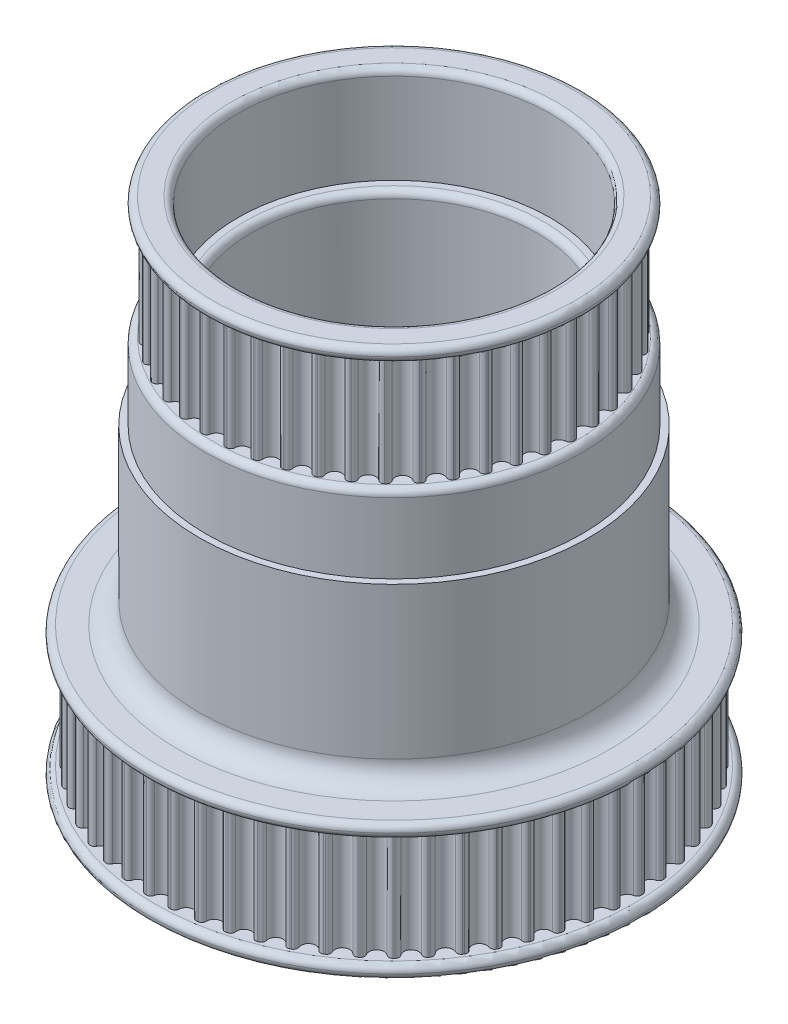
SolidWorks part; units mm, degrees
ref_plane "Front Plane" through (0, 0, 0) normal (0, 0, 1) x (1, 0, 0)
ref_plane "Top Plane" through (0, 0, 0) normal (0, 1, 0) x (1, 0, 0)
ref_plane "Right Plane" through (0, 0, 0) normal (1, 0, 0) x (0, 0, -1)
sketch "PulleyOffsets" plane through (0, 0, 0) normal (1, 0, 0) x (0, 0, -1)
  line L0 (22.225, 0) -> (-22.225, 0) construction
  line L1 (22.225, 44.45) -> (-22.225, 44.45) construction
  line L2 (0, 0) -> (0, 44.45) construction
  point P7 (0, 0)
  dimension "D1" = 44.45
ref_axis "Axis1" through (0, 34.9332, 0) along (0, -1, 0)
ref_plane "Big Pulley Plane" through (0, 0, 0) normal (0, 1, 0) x (1, 0, 0)
ref_plane "Small Pulley Plane" through (0, 44.45, 0) normal (0, 1, 0) x (1, 0, 0)
sketch "Sketch1" plane through (0, 0, 0) normal (0, 1, 0) x (1, 0, 0)
  line L0 (0, 0) -> (0, 28.2667) construction
  line L1 (0, 0) -> (2.9202, 27.7837) construction
  circle A0 centre (0, 0) radius 28.2667 construction
  circle A1 centre (0, 0) radius 27.0467 construction
  circle A2 centre (0, 27.9367) radius 0.89 construction
  circle A5 centre (2.9202, 27.7837) radius 0.89 construction
  arc A6 (0, 27.0467) -> (0.8804, 27.8061) centre (0, 27.9367) ccw
  arc A7 (0.8804, 27.8061) -> (1.3997, 28.2321) centre (1.3749, 27.7327) cw
  arc A8 (1.559, 28.2237) -> (2.031, 27.7458) centre (1.5314, 27.7245) cw
  arc A9 (2.8272, 26.8986) -> (2.031, 27.7458) centre (2.9202, 27.7837) cw
  arc A10 (1.3997, 28.2321) -> (1.559, 28.2237) centre (0, 0) cw
  arc A11 (0, 27.0467) -> (2.8272, 26.8986) centre (0, 0) ccw
  dimension "D1" = 56.5335
  dimension "D3" = 1.78
  dimension "D4" = 0.5
  dimension "D2" = 1.22
  dimension "D5" = 6
extrude "Boss-Extrude1" add sketch "Sketch1" along normal mid plane 13 contours A6 A11 A9 A8 A7 region at (0.001, 0, -0.0192)
pattern_circular "CirPattern1" count 60 over 360 about axis through (0, 34.9332, 0) along (0, -1, 0) of "Boss-Extrude1"
sketch "Sketch2" plane through (0, 0, 0) normal (1, 0, 0) x (0, 0, -1)
  line L10 (0, 6.5) -> (29.4415, 6.5) construction
  line L11 (0, 6.5) -> (0, 8.0875) construction
  line L12 (0, 8.0875) -> (29.4415, 8.0875) construction
  line L15 (29.4415, 6.5) -> (29.4415, 8.0875) construction
  line L20 (0, 34.9332) -> (0, -6.9932) construction
  line L22 (29.4415, 8.0875) -> (0, 8.0875)
  line L23 (29.4415, 8.0875) -> (29.4415, 6.5)
  line L24 (29.4415, 6.5) -> (0, 6.5)
  line L25 (0, 8.0875) -> (0, 6.5)
  dimension "D1" = 1.5875
  dimension "D2" = 29.4415
  dimension "D3" = 6.5
revolve "Revolve3" add sketch "Sketch2" angle 360 about axis through (0, 34.9332, 0) along (0, -1, 0) region at (0, 7.2937, -14.7207)
mirror "Mirror1" about plane through (0, 0, 0) normal (0, 1, 0) of "Revolve3"
sketch "Sketch6" plane through (0, 0, 0) normal (0, 1, 0) x (1, 0, 0)
  line L0 (0, 0) -> (0, 21.582) construction
  line L1 (0, 0) -> (2.8938, 21.0541) construction
  circle A0 centre (0, 0) radius 21.582 construction
  circle A1 centre (0, 0) radius 20.362 construction
  circle A2 centre (0, 21.252) radius 0.89 construction
  circle A5 centre (2.8938, 21.0541) radius 0.89 construction
  arc A6 (0, 20.362) -> (0.8793, 21.1145) centre (0, 21.252) ccw
  arc A7 (0.8793, 21.1145) -> (1.4059, 21.5362) centre (1.3733, 21.0373) cw
  arc A8 (1.5397, 21.527) -> (2.004, 21.0376) centre (1.5041, 21.0283) cw
  arc A9 (2.7726, 20.1724) -> (2.004, 21.0376) centre (2.8938, 21.0541) cw
  arc A10 (1.4059, 21.5362) -> (1.5397, 21.527) centre (0, 0) cw construction
  arc A11 (0, 20.362) -> (2.7726, 20.1724) centre (0, 0) ccw
  arc A12 (1.4059, 21.5362) -> (1.5397, 21.527) centre (0, 0) cw
  dimension "D3" = 1.78
  dimension "D4" = 0.5
  dimension "D2" = 1.22
  dimension "D1" = 43.1641
  dimension "D5" = 7.826
extrude "Boss-Extrude2" add sketch "Sketch6" along normal mid plane 13 from surface contours A6 A11 A9 A8 A7 region at (0.0017, 0, -0.025) starting at plane "Small Pulley Plane"
pattern_circular "CirPattern2" count 46 over 360 about axis through (0, 34.9332, 0) along (0, -1, 0) of "Boss-Extrude2"
sketch "Sketch9" plane through (0, 0, 0) normal (1, 0, 0) x (0, 0, -1)
  line L1 (0, 37.95) -> (22.7568, 37.95)
  line L2 (0, 37.95) -> (0, 36.3625)
  line L3 (0, 36.3625) -> (22.7568, 36.3625)
  line L4 (22.7568, 37.95) -> (22.7568, 36.3625)
  line L6 (0, 50.95) -> (22.7568, 50.95)
  line L7 (0, 50.95) -> (0, 52.5375)
  line L8 (0, 52.5375) -> (22.7568, 52.5375)
  line L9 (22.7568, 50.95) -> (22.7568, 52.5375)
  line L10 (29.4415, 8.0875) -> (29.4415, 6.5) construction
  line L11 (0, 34.9332) -> (0, -6.9932) construction
  line L12 (21.1145, 50.95) -> (20.362, 50.95) construction
  line L13 (20.1641, 37.95) -> (21.0376, 37.95) construction
  dimension "D1" = 22.7568
revolve "Revolve4" add sketch "Sketch9" angle 360 about axis through (0, 34.9332, 0) along (0, -1, 0)
sketch "Sketch10" plane through (0, -8.0875, 0) normal (0, -1, 0) x (1, 0, 0)
  circle A0 centre (0, 0) radius 18.669
  dimension "D1" = 37.338
extrude "Cut-Extrude1" cut sketch "Sketch10" against normal through all
sketch "Sketch11" plane through (0, 52.5375, 0) normal (0, 1, 0) x (1, 0, 0)
  circle A0 centre (0, 0) radius 22.5
  dimension "D1" = 45
extrude "Cut-Extrude2" cut sketch "Sketch11" against normal up to surface (16.175 mm away) flip side to cut up to face at (0, 36.3625, 18.669)
sketch "Sketch12" plane through (0, 0, 0) normal (0, 0, 1) x (1, 0, 0)
  line L0 (29.4415, 8.0875) -> (-29.4415, 8.0875) construction
  line L1 (18.669, 36.3625) -> (22.5, 36.3625)
  line L2 (18.669, 36.3625) -> (18.669, 8.0875) construction
  line L3 (18.669, 8.0875) -> (22.5, 8.0875)
  line L4 (22.5, 36.3625) -> (22.5, 8.0875) construction
  line L5 (22.5, 36.3625) -> (22.5, 37.95) construction
  line L6 (22.5, 28.7425) -> (22.5, 36.3625)
  line L7 (22.5, 28.7425) -> (23.2938, 28.7425)
  line L8 (22.5, 28.7425) -> (22.5, 8.0875) construction
  line L9 (22.5, 8.0875) -> (23.2938, 8.0875)
  line L10 (23.2938, 28.7425) -> (23.2938, 8.0875)
  line L11 (18.669, -8.0875) -> (18.669, 8.0875) construction
  line L12 (18.669, 2.0875) -> (17.0815, 2.0875)
  line L13 (18.669, 2.0875) -> (18.669, 40.95) construction
  line L14 (18.669, 40.95) -> (17.0815, 40.95)
  line L15 (17.0815, 2.0875) -> (17.0815, 40.95)
  line L16 (-29.4415, -8.0875) -> (29.4415, -8.0875) construction
  line L18 (18.669, 2.0875) -> (18.669, 8.0875)
  line L19 (18.669, 36.3625) -> (18.669, 40.95)
  line L20 (32.3856, 44.45) -> (-32.3856, 44.45) construction
  dimension "D1" = 7.62
  dimension "D2" = 0.7937
  dimension "D3" = 10.175
  dimension "D5" = 1.5875
  dimension "D4" = 3.5
revolve "Revolve5" add sketch "Sketch12" angle 360 about axis through (0, 34.9332, 0) along (0, -1, 0)
fillet "Fillet1" radius 2.54 1 edges at (0, 8.0875, -23.2938)
fillet "Fillet2" radius 0.7937 11 edges at (0, 40.95, 17.0815) (0, 52.5375, -18.669) (0, -8.0875, -18.669) (0, 2.0875, 17.0815) (0, -8.0875, 29.4415) (0, 8.0875, 29.4415) (0, 52.5375, 22.5) (0, 50.95, 22.5) (0, 37.95, -22.5) (0, 6.5, 29.4415) (0, -6.5, 29.4415)
equation "\"TEETH_NUM\"= 60"
equation "\"TOOTH_PITCH\"= 3mm"
equation "\"PITCH_LINE_OFFSET\"= .015in"
equation "\"DIAMETER_PER_GROOVE\"= \"OUTSIDE_DIAMETER\" / \"TEETH_NUM\" * 1in"
equation "\"PITCH_DIAMETER\"= ( ( \"TEETH_NUM\" * 3 - 1.31 ) / 3.1415 + .415 ) * 1mm"
equation "\"OUTSIDE_DIAMETER\"= \"PITCH_DIAMETER\" - \"PITCH_LINE_OFFSET\" * 2"
equation "\"D1@Sketch1\"=\"OUTSIDE_DIAMETER\""
equation "\"TOOTH_HEIGHT\"= 1.22mm"
equation "\"D2@Sketch1\"=\"TOOTH_HEIGHT\""
equation "\"TOOTH_DIAMETER\"= 1.78mm"
equation "\"INTERNAL_RADIUS\"= .5mm"
equation "\"D3@Sketch1\"=\"TOOTH_DIAMETER\""
equation "\"D5@Sketch1\"=360 / \"TEETH_NUM\""
equation "\"D4@Sketch1\"=\"INTERNAL_RADIUS\""
equation "\"D1@CirPattern1\"=\"TEETH_NUM\""
equation "\"BELT_GAP\"= 13mm"
equation "\"D2@Sketch2\"=\"PITCH_DIAMETER\"/2+1/32"
equation "\"D3@Sketch2\"=\"BELT_GAP\"/2"
equation "\"2_TEETH_NUM\"= 46"
equation "\"2_PITCH_DIAMETER\"= ( ( \"2_TEETH_NUM\" * 3 - 1.31 ) / 3.1415 + .415 ) * 1mm"
equation "\"2_OUTSIDE_DIAMETER\"= \"2_PITCH_DIAMETER\" - \"PITCH_LINE_OFFSET\" * 2"
equation "\"2_DIAMETER_PER_GROOVE\"= \"2_OUTSIDE_DIAMETER\" / \"2_TEETH_NUM\" * 1in"
equation "\"D5@Sketch6\"=360/\"2_TEETH_NUM\""
equation "\"D1@Sketch6\"=\"2_OUTSIDE_DIAMETER\""
equation "\"D2@Sketch6\"=\"TOOTH_HEIGHT\""
equation "\"D3@Sketch6\"=\"TOOTH_DIAMETER\""
equation "\"D4@Sketch6\"=\"INTERNAL_RADIUS\""
equation "\"2_BELT_GAP\"= 13mm"
equation "\"D1@CirPattern2\"=\"2_TEETH_NUM\""
equation "\"D1@Boss-Extrude2\"=\"2_BELT_GAP\""
equation "\"Pulley_OffSets\"= 1.75"
equation "\"D1@PulleyOffsets\" = \"Pulley_OffSets\""
equation "\"D1@Boss-Extrude1\"=\"BELT_GAP\""
equation "\"D1@Sketch9\"=\"2_PITCH_DIAMETER\"/2+1/32"
equation "\"bearing_hole_depth_arm_side\"= 7mm + .125in"
equation "\"D3@Sketch12\"=\"bearing_hole_depth_arm_side\""
